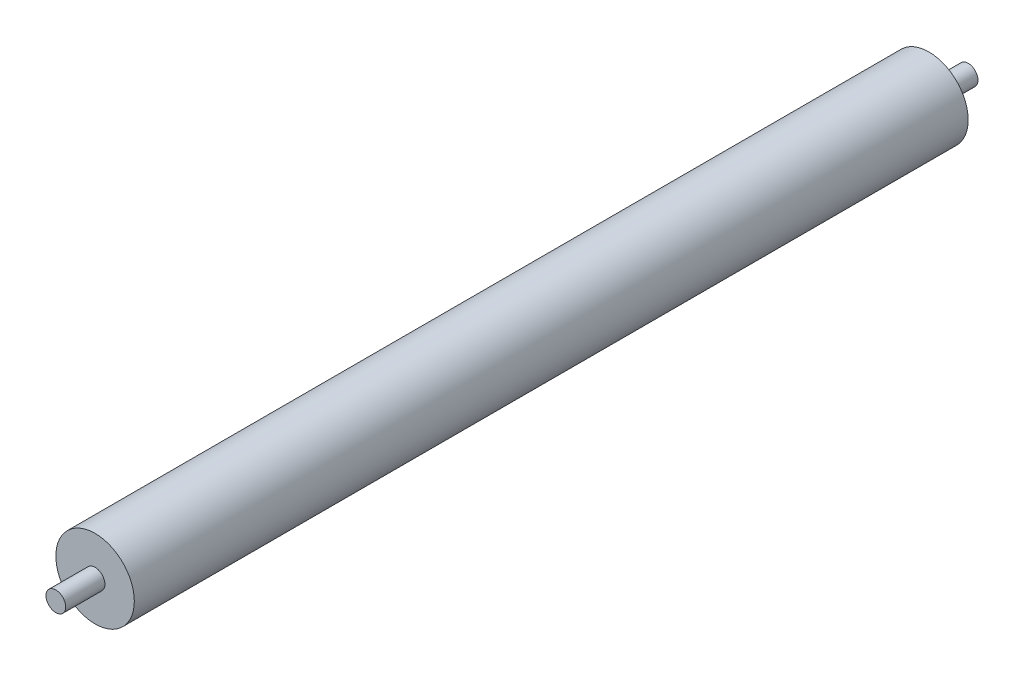
SolidWorks part; units mm, degrees
material "Rubber"
ref_plane "Front Plane" through (0, 0, 0) normal (0, 0, 1) x (1, 0, 0)
ref_plane "Top Plane" through (0, 0, 0) normal (0, 1, 0) x (1, 0, 0)
ref_plane "Right Plane" through (0, 0, 0) normal (1, 0, 0) x (0, 0, -1)
sketch "Sketch1" plane through (0, 0, 0) normal (0, 0, 1) x (1, 0, 0)
  circle A0 centre (0, 0) radius 25.4
extrude "Boss-Extrude1" add sketch "Sketch1" along normal blind 590.55 contours A0
sketch "Sketch2" plane through (0, 0, 0) normal (0, 0, 1) x (1, 0, 0)
  circle A0 centre (0, 0) radius 6.3619
extrude "Cut-Extrude1" cut sketch "Sketch2" along normal blind 25.4 flip side to cut contours A0
sketch "Sketch5" plane through (0, 0, 590.55) normal (0, 0, 1) x (1, 0, 0)
  circle A0 centre (0, 0) radius 6.3779
extrude "Cut-Extrude4" cut sketch "Sketch5" against normal blind 25.4 flip side to cut
shell "Shell3" thickness 5.08
